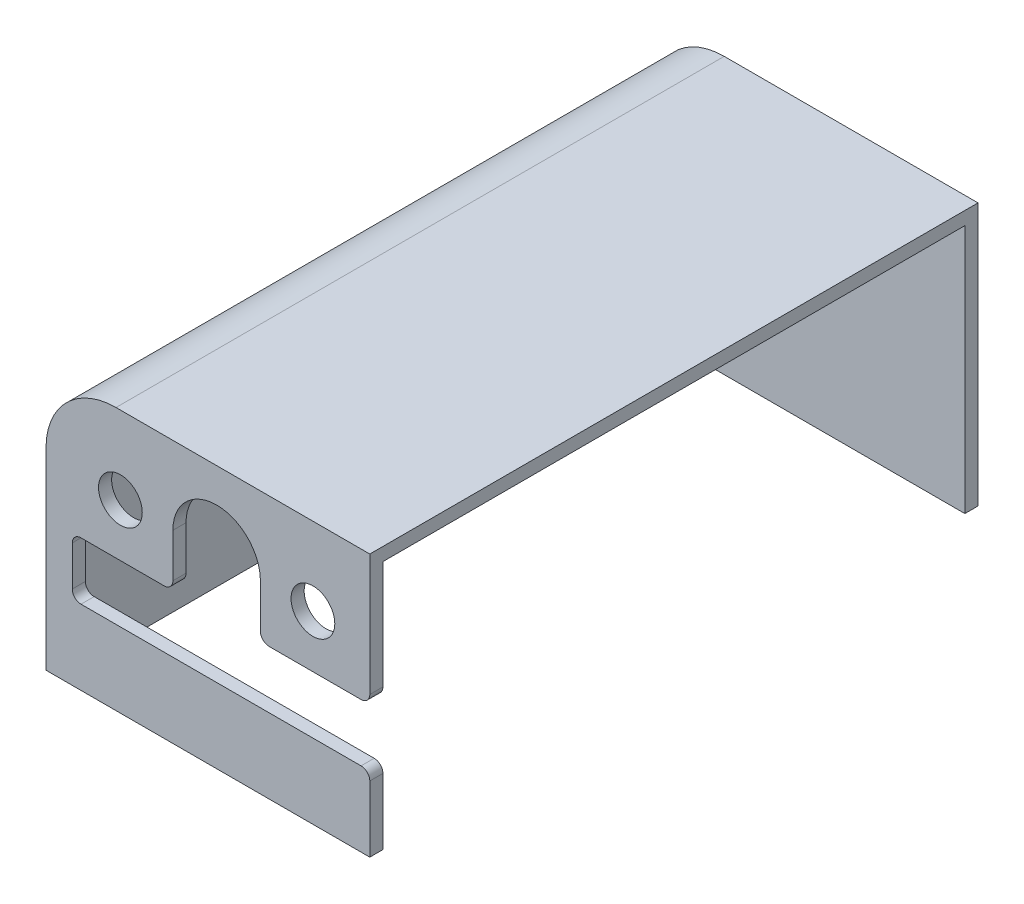
SolidWorks part; units mm, degrees
ref_plane "Front Plane" through (0, 0, 0) normal (0, 0, 1) x (1, 0, 0)
ref_plane "Top Plane" through (0, 0, 0) normal (0, 1, 0) x (1, 0, 0)
ref_plane "Right Plane" through (0, 0, 0) normal (1, 0, 0) x (0, 0, -1)
sketch "Sketch1" plane through (0, 0, 0) normal (0, 1, 0) x (1, 0, 0)
  line L0 (17.5, 35.5) -> (-18, 35.5)
  line L1 (-17.5, 35) -> (17.5, 35) construction
  line L2 (-17.5, 35) -> (-17.5, -35) construction
  line L3 (-17.5, -35) -> (17.5, -35) construction
  line L4 (17.5, 35) -> (17.5, -35) construction
  line L5 (-17.5, 35) -> (17.5, -35) construction
  line L6 (-17.5, -35) -> (17.5, 35) construction
  line L7 (-18, 35.5) -> (-18, -35.5)
  line L8 (-18, -35.5) -> (17.5, -35.5)
  line L9 (17.5, 37) -> (-19.5, 37)
  line L10 (-19.5, 37) -> (-19.5, -37)
  line L11 (-19.5, -37) -> (17.5, -37)
  line L12 (17.5, -35.5) -> (17.5, -37)
  line L13 (17.5, 37) -> (17.5, 35.5)
  point P0 (0, 0)
  dimension "D1" = 35
  dimension "D2" = 70
  dimension "D3" = 0.5
  dimension "D4" = 0.5
  dimension "D5" = 0.5
  dimension "D6" = 1.5
extrude "Boss-Extrude1" add sketch "Sketch1" along normal blind 15
sketch "Sketch2" plane through (0, 15, 0) normal (0, 1, 0) x (1, 0, 0)
  line L0 (-4, -27.5) -> (4, -27.5)
  line L1 (-19.5, -37) -> (28.4228, -37)
  line L2 (-19.5, -37) -> (-19.5, -32.5)
  line L3 (-19.5, -32.5) -> (28.4228, -32.5)
  line L4 (28.4228, -37) -> (28.4228, -32.5)
  line M5 (-19.5, 37) -> (-19.5, -37)
  line M6 (-19.5, -37) -> (17.5, -37)
  line M7 (17.5, -37) -> (17.5, -35.5)
  line M8 (17.5, -35.5) -> (-18, -35.5)
  line M9 (-18, -35.5) -> (-18, 35.5)
  dimension "D1" = 5
extrude "Cut-Extrude1" cut sketch "Sketch2" against normal through all both and the other way through all contours L1 L4 L3 M9 M8 M7 | L3 M5 M6 M7 M8 M9 region at (-2.3313, 15, 36.0812) region at (7.0798, 15, 34.2368)
sketch "Sketch3" plane through (0, 15, 0) normal (0, 1, 0) x (1, 0, 0)
  line L0 (17.5, 35.5) -> (17.5, 37) construction
  line L1 (-18, -32.5) -> (17.5, -32.5)
  line L2 (-18, -32.5) -> (-18, -31)
  line L3 (-18, -31) -> (17.5, -31)
  line L4 (17.5, -32.5) -> (17.5, -31)
  dimension "D1" = 1.5
extrude "Boss-Extrude2" add sketch "Sketch3" against normal up to vertex (15 mm away) up to point (-19.5, 0, 32.5)
sketch "Sketch4" plane through (0, 15, 0) normal (0, 1, 0) x (1, 0, 0)
  line L8 (-19.5, -32.5) -> (17.5, -32.5)
  line L10 (-19.5, -32.5) -> (17.5, -32.5)
  line L11 (-18, -31) -> (-18, 35.5)
  line L12 (-18, 35.5) -> (17.5, 35.5)
  line L13 (17.5, 35.5) -> (17.5, 37)
  line L14 (17.5, 37) -> (-19.5, 37)
  line L15 (-19.5, 37) -> (-19.5, -32.5)
  line L19 (-18, -31) -> (-18, 35.5)
  line L20 (-18, 35.5) -> (17.5, 35.5)
  line L21 (17.5, 35.5) -> (17.5, 37)
  line L22 (17.5, 37) -> (-19.5, 37)
  line L23 (-19.5, 37) -> (-19.5, -32.5)
  line L25 (17.5, -32.5) -> (17.5, -31)
  line L27 (17.5, -32.5) -> (17.5, -31)
  line L28 (17.5, -31) -> (-18, -31)
  line L29 (17.5, -31) -> (-18, -31)
  dimension "D1" = 0
extrude "Boss-Extrude3" add sketch "Sketch4" along normal blind 13.5
sketch "Sketch5" plane through (0, 28.5, 0) normal (0, 1, 0) x (1, 0, 0)
  line L1 (17.5, 37) -> (-19.5, 37)
  line L2 (17.5, 37) -> (17.5, -32.5)
  line L3 (17.5, -32.5) -> (-19.5, -32.5)
  line L4 (-19.5, 37) -> (-19.5, -32.5)
extrude "Boss-Extrude4" add sketch "Sketch5" along normal blind 1.5
fillet "Fillet1" radius 8 2 edges at (-18, 28.5, -2.25) (-19.5, 30, -2.25)
sketch "Sketch6" plane through (0, 0, 32.5) normal (0, 0, 1) x (1, 0, 0)
  line L0 (17.5, 0) -> (17.5, 30) construction
  line L5 (-16.5, 15.1) -> (17.5, 15.1)
  line L6 (-16.5, 15.1) -> (-16.5, 10.1)
  line L8 (17.5, 15.1) -> (17.5, 10.1)
  line L9 (-16.5, 15.1) -> (17.5, 10.1) construction
  line L10 (0.5, 12.6) -> (17.5, 15.1) construction
  line L11 (-19.5, 0) -> (-19.5, 22) construction
  line L12 (-12.5, 12.6) -> (12.5, 12.6) construction
  line L13 (5, 15.1) -> (5, 21.1)
  line L14 (-5, 21.1) -> (-5, 15.1)
  line L15 (-11, 21.1) -> (11, 21.1) construction
  line L16 (-16.5, 10.1) -> (-16.5, 8.5372)
  line L17 (-16.5, 8.5372) -> (17.5, 8.5372)
  line L18 (17.5, 8.5372) -> (17.5, 10.1)
  arc A0 (5, 21.1) -> (-5, 21.1) centre (0, 21.1) ccw
  circle A1 centre (-11, 21.1) radius 2.5
  circle A2 centre (11, 21.1) radius 2.5
  point P0 (0.5, 12.6)
  point P23 (0, 21.1)
  line M9 (17.5, 0) -> (17.5, 30)
  dimension "D3" = 5
  dimension "D5" = 5
  dimension "D1" = 3
  dimension "D2" = 5
  dimension "D4" = 6
  dimension "D6" = 22
extrude "Cut-Extrude2" cut sketch "Sketch6" against normal blind 1.5 contours L13 A0 L14 L5 | L6 L5 M9 | A2 | A1 region at (0.5, 11.8186, 32.5) region at (0, 20.1262, 32.5) region at (-11, 21.1, 32.5) region at (11, 21.1, 32.5)
fillet "Fillet2" radius 1 6 edges at (17.5, 15.1, 31.75) (-16.5, 15.1, 31.75) (5, 15.1, 31.75) (-5, 15.1, 31.75) (17.5, 8.5372, 31.75) (-16.5, 8.5372, 31.75)
sketch "Sketch7" plane through (-19.5, 0, 0) normal (-1, 0, 0) x (0, 0, 1)
  circle A0 centre (25, 1.5) radius 0.75
  circle A1 centre (0, 1.5) radius 0.75
  circle A2 centre (-25, 1.5) radius 0.75
extrude "Cut-Extrude3" cut sketch "Sketch7" against normal through all both and the other way through all
